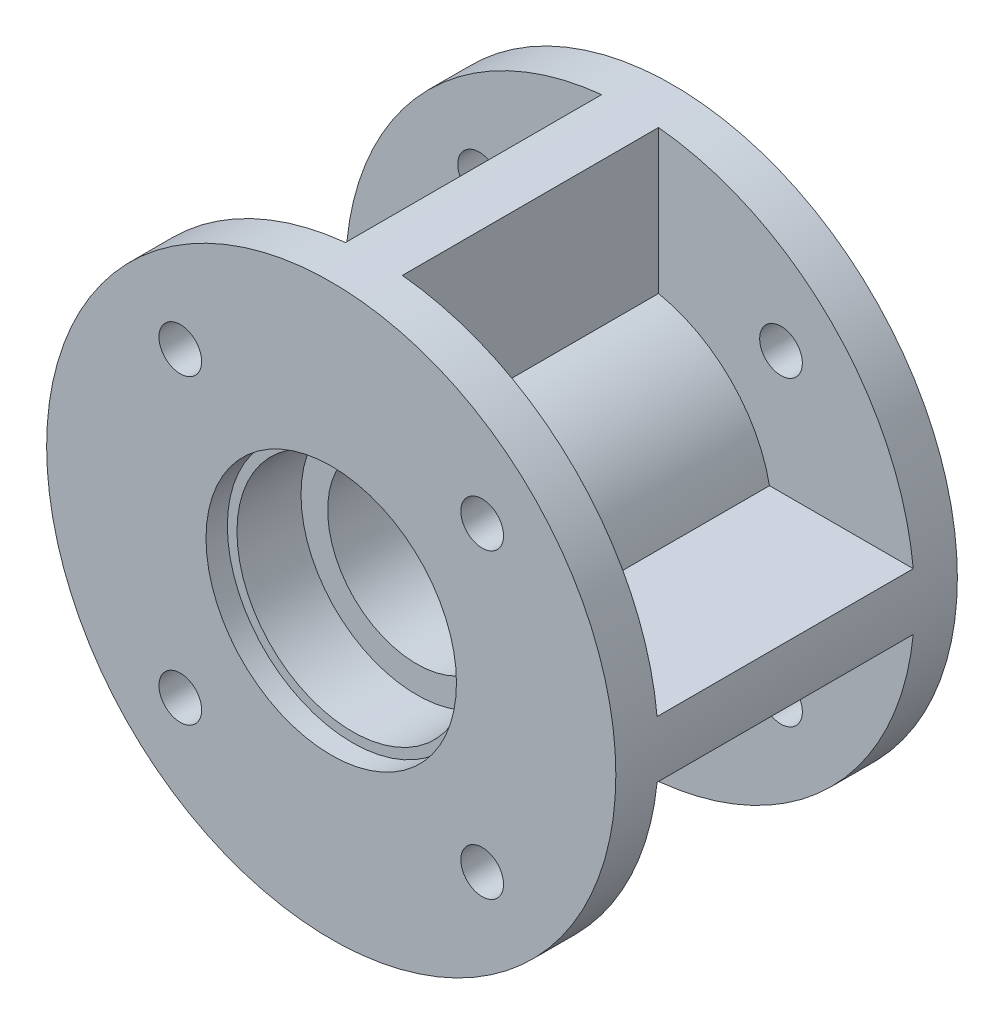
SolidWorks part; units mm, degrees
ref_plane "Front Plane" through (0, 0, 0) normal (0, 0, 1) x (1, 0, 0)
ref_plane "Top Plane" through (0, 0, 0) normal (0, 1, 0) x (1, 0, 0)
ref_plane "Right Plane" through (0, 0, 0) normal (1, 0, 0) x (0, 0, -1)
sketch "Sketch1" plane through (0, 0, 0) normal (0, 0, 1) x (1, 0, 0)
  circle A0 centre (0, 0) radius 12.5
  circle A1 centre (0, 0) radius 40
  dimension "D1" = 80
  dimension "D2" = 25
extrude "Boss-Extrude1" add sketch "Sketch1" along normal blind 6
sketch "Sketch2" plane through (0, 0, 6) normal (0, 0, 1) x (1, 0, 0)
  circle A0 centre (0, 0) radius 20
  circle A1 centre (0, 0) radius 12.5
  dimension "D1" = 40
extrude "Boss-Extrude2" add sketch "Sketch2" along normal blind 30
sketch "Sketch6" plane through (0, 0, 36) normal (0, 0, 1) x (1, 0, 0)
  circle A0 centre (0, 0) radius 20
  circle A1 centre (0, 0) radius 16.25
  dimension "D1" = 32.5
extrude "Boss-Extrude5" add sketch "Sketch6" along normal blind 12
sketch "Sketch8" plane through (0, 0, 6) normal (0, 0, 1) x (1, 0, 0)
  line L0 (4, -39.7995) -> (4, -19.5959)
  line L2 (39.7995, 4) -> (19.5959, 4)
  line L4 (19.5959, -4) -> (39.7995, -4)
  line L5 (20, 0) -> (40, 0) construction
  line L6 (-4, -19.5959) -> (-4, -39.7995)
  line L7 (-39.7995, -4) -> (-19.5959, -4)
  line L8 (-19.5959, 4) -> (-39.7995, 4)
  line L9 (-4, 39.7995) -> (-4, 19.5959)
  line L10 (4, 19.5959) -> (4, 39.7995)
  circle A0 centre (0, 0) radius 40 construction
  arc A1 (19.5959, -4) -> (19.5959, 4) centre (0, 0) ccw
  arc A2 (39.7995, -4) -> (39.7995, 4) centre (0, 0) ccw
  arc A3 (-4, -19.5959) -> (4, -19.5959) centre (0, 0) ccw
  arc A4 (-4, -39.7995) -> (4, -39.7995) centre (0, 0) ccw
  arc A5 (-19.5959, 4) -> (-19.5959, -4) centre (0, 0) ccw
  arc A6 (-39.7995, 4) -> (-39.7995, -4) centre (0, 0) ccw
  arc A7 (4, 19.5959) -> (-4, 19.5959) centre (0, 0) ccw
  arc A8 (4, 39.7995) -> (-4, 39.7995) centre (0, 0) ccw
  point P9 (40, 0)
  point P26 (0, 0)
  dimension "D1" = 4
extrude "Boss-Extrude6" add sketch "Sketch8" along normal up to surface (42 mm away) up to face at (20, 0, 48)
sketch "Sketch9" plane through (0, 0, 48) normal (0, 0, 1) x (1, 0, 0)
  circle A0 centre (0, 0) radius 17.6
  dimension "D1" = 35.2
extrude "Cut-Extrude1" cut sketch "Sketch9" against normal blind 3
sketch "Sketch11" plane through (0, 0, 48) normal (0, 0, 1) x (1, 0, 0)
  circle A0 centre (0, 0) radius 40
  circle A1 centre (0, 0) radius 20
extrude "Boss-Extrude14" add sketch "Sketch11" against normal blind 6 contours A0 | A1
sketch "Sketch12" plane through (0, 0, 0) normal (0, 0, -1) x (-1, 0, 0)
  line L0 (0, 0) -> (-54.2872, 0) construction
  line L1 (0, 0) -> (-21.2132, 21.2132) construction
  circle A0 centre (-21.2132, 21.2132) radius 3
  circle A1 centre (21.2132, 21.2132) radius 3
  circle A2 centre (21.2132, -21.2132) radius 3
  circle A3 centre (-21.2132, -21.2132) radius 3
  point P16 (0, 0)
  dimension "D3" = 6
  dimension "D1" = 45
  dimension "D2" = 30
  dimension "D4" = 4
extrude "Cut-Extrude2" cut sketch "Sketch12" against normal blind 78
